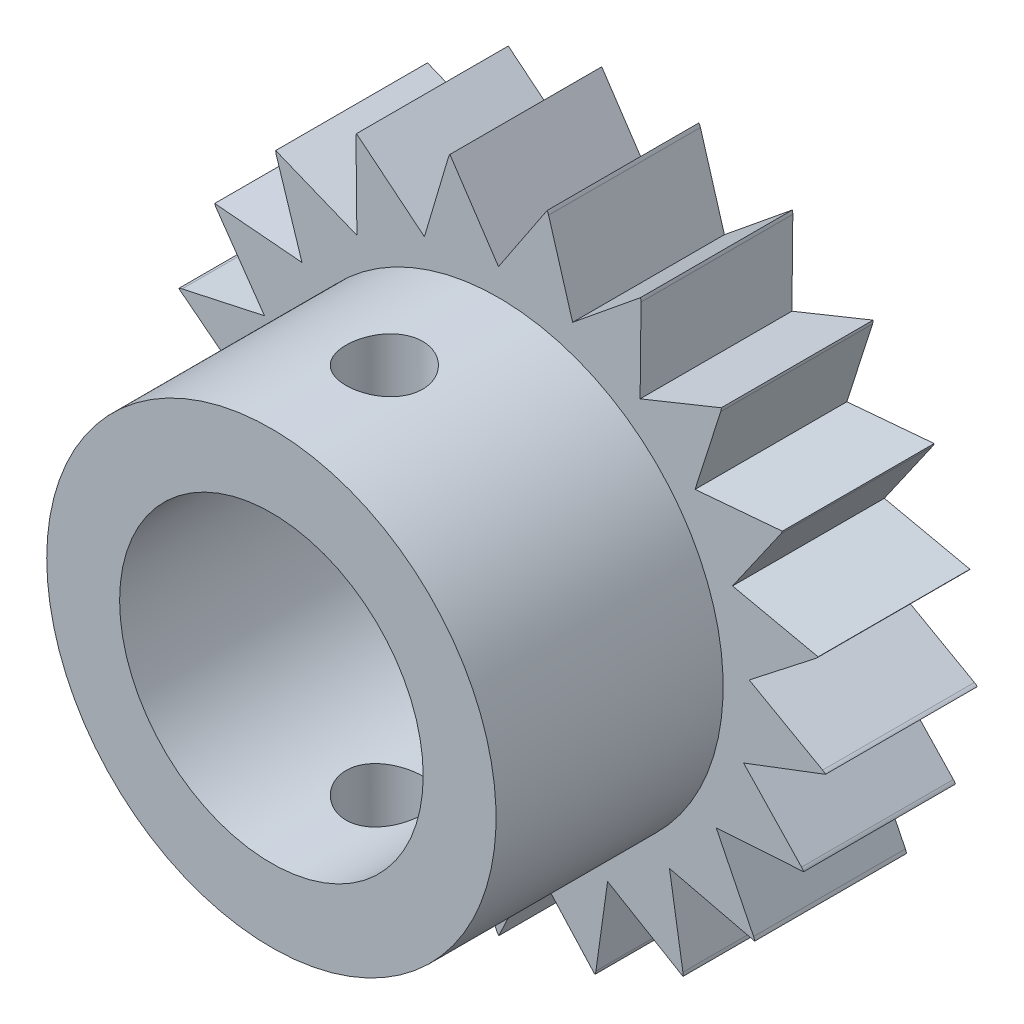
SolidWorks part; units mm, degrees
ref_plane "Front Plane" through (0, 0, 0) normal (0, 0, 1) x (1, 0, 0)
ref_plane "Top Plane" through (0, 0, 0) normal (0, 1, 0) x (1, 0, 0)
ref_plane "Right Plane" through (0, 0, 0) normal (1, 0, 0) x (0, 0, -1)
sketch "Sketch2" plane through (0, 0, 0) normal (1, 0, 0) x (0, 0, -1)
  line L0 (0, 3.175) -> (0, 6.858)
  line L1 (0, 6.858) -> (-3.175, 6.858)
  line L2 (-3.175, 6.858) -> (-3.175, 4.699)
  line L3 (-3.175, 4.699) -> (-7.9248, 4.699)
  line L4 (-7.9248, 4.699) -> (-7.9248, 3.175)
  line L5 (-7.9248, 3.175) -> (0, 3.175)
  line L6 (6.7854, 0) -> (-20.99, 0) construction
  dimension "D1" = 3.175
  dimension "D2" = 3.175
  dimension "D3" = 7.9248
  dimension "D4" = 4.699
  dimension "D5" = 6.858
revolve "Revolve1" add sketch "Sketch2" angle 360 about L6
sketch "Sketch5" plane through (0, 0, 3.175) normal (0, 0, 1) x (1, 0, 0)
  line L0 (0, 0) -> (0, 10.1517) construction
  line L1 (1.5498, 5.0242) -> (1.0283, 6.7805)
  line L2 (0, 5.2578) -> (1.016, 6.7823)
  line L3 (0, 5.2578) -> (-1.016, 6.7823)
  line L4 (1.5498, 5.0242) -> (2.97, 6.1815)
  line L5 (2.9618, 4.3442) -> (2.9812, 6.1762)
  line L6 (2.9618, 4.3442) -> (4.6601, 5.0315)
  line L7 (4.1107, 3.2782) -> (4.6692, 5.0231)
  line L8 (4.1107, 3.2782) -> (5.9361, 3.4344)
  line L9 (4.8943, 1.9209) -> (5.9423, 3.4236)
  line L10 (4.8943, 1.9209) -> (6.6847, 1.5321)
  line L11 (5.2431, 0.3929) -> (6.6874, 1.52)
  line L12 (5.2431, 0.3929) -> (6.8393, -0.5063)
  line L13 (5.126, -1.17) -> (6.8384, -0.5187)
  line L14 (5.126, -1.17) -> (6.3862, -2.4997)
  line L15 (4.5534, -2.6289) -> (6.3817, -2.5113)
  line L16 (4.5534, -2.6289) -> (5.3657, -4.271)
  line L17 (3.5762, -3.8542) -> (5.3579, -4.2807)
  line L18 (3.5762, -3.8542) -> (3.8684, -5.6629)
  line L19 (2.2813, -4.7371) -> (3.8581, -5.6698)
  line L20 (2.2813, -4.7371) -> (2.0274, -6.5515)
  line L21 (0.7836, -5.1991) -> (2.0155, -6.5551)
  line L22 (0.7836, -5.1991) -> (0.0062, -6.858)
  line L23 (-0.7836, -5.1991) -> (-0.0062, -6.858)
  line L24 (-0.7836, -5.1991) -> (-2.0155, -6.5551)
  line L25 (-2.2813, -4.7371) -> (-2.0274, -6.5515)
  line L26 (-2.2813, -4.7371) -> (-3.8581, -5.6698)
  line L27 (-3.5762, -3.8542) -> (-3.8684, -5.6629)
  line L28 (-3.5762, -3.8542) -> (-5.3579, -4.2807)
  line L29 (-4.5534, -2.6289) -> (-5.3657, -4.271)
  line L30 (-4.5534, -2.6289) -> (-6.3817, -2.5113)
  line L31 (-5.126, -1.17) -> (-6.3862, -2.4997)
  line L32 (-5.126, -1.17) -> (-6.8384, -0.5187)
  line L33 (-5.2431, 0.3929) -> (-6.8393, -0.5063)
  line L34 (-5.2431, 0.3929) -> (-6.6874, 1.52)
  line L35 (-4.8943, 1.9209) -> (-6.6847, 1.5321)
  line L36 (-4.8943, 1.9209) -> (-5.9423, 3.4236)
  line L37 (-4.1107, 3.2782) -> (-5.9361, 3.4344)
  line L38 (-4.1107, 3.2782) -> (-4.6692, 5.0231)
  line L39 (-2.9618, 4.3442) -> (-4.6601, 5.0315)
  line L40 (-2.9618, 4.3442) -> (-2.9812, 6.1762)
  line L41 (-1.5498, 5.0242) -> (-2.97, 6.1815)
  line L42 (-1.5498, 5.0242) -> (-1.0283, 6.7805)
  circle A0 centre (0, 0) radius 6.858 construction
  circle M2 centre (0, 0) radius 6.858
  dimension "D1" = 5.2578
  dimension "D2" = 1.016
  dimension "D3" = 2.032
  dimension "D4" = 21
extrude "Cut-Extrude5" cut sketch "Sketch5" against normal through all and the other way through all contours L41 L42 M2 | L39 L40 M2 | L37 L38 M2 | L35 L36 M2 | L33 L34 M2 | L31 L32 M2 | L29 L30 M2 | L27 L28 M2 | L25 L26 M2 | L23 L24 M2 | L21 L22 M2 | L19 L20 M2 | L17 L18 M2 | L15 L16 M2 | L13 L14 M2 | L11 L12 M2 | L9 L10 M2 | L7 L8 M2 | L5 L6 M2 | L1 L4 M2 | L0 L2 M2 | L3 L0 M2 region at (-0.3413, 6.3076, 3.175) region at (0.3413, 6.3076, 3.175) region at (1.8592, 6.0274, 3.175) region at (-1.8592, 6.0274, 3.175) region at (3.5532, 5.2116, 3.175) region at (-3.5532, 5.2116, 3.175) region at (4.9315, 3.9327, 3.175) region at (-4.9315, 3.9327, 3.175) region at (5.8716, 2.3044, 3.175) region at (-5.8716, 2.3044, 3.175) region at (6.29, 0.4714, 3.175) region at (-6.29, 0.4714, 3.175) region at (-6.1495, -1.4036, 3.175) region at (6.1495, -1.4036, 3.175) region at (-5.4626, -3.1538, 3.175) region at (5.4626, -3.1538, 3.175) region at (-4.2903, -4.6238, 3.175) region at (4.2903, -4.6238, 3.175) region at (-2.7368, -5.683, 3.175) region at (2.7368, -5.683, 3.175) region at (-0.9401, -6.2372, 3.175) region at (0.9401, -6.2372, 3.175)
fillet "Fillet1" radius 0.254 21 edges at (1.0283, 6.7805, 1.5875) (2.9812, 6.1762, 1.5875) (4.6692, 5.0231, 1.5875) (5.9423, 3.4236, 1.5875) (6.6874, 1.52, 1.5875) (6.8393, -0.5063, 1.5875) (6.3862, -2.4997, 1.5875) (5.3657, -4.271, 1.5875) (3.8684, -5.6629, 1.5875) (2.0274, -6.5515, 1.5875) (-0.0062, -6.858, 1.5875) (-2.0274, -6.5515, 1.5875) (-3.8684, -5.6629, 1.5875) (-5.3657, -4.271, 1.5875) (-6.3862, -2.4997, 1.5875) (-6.8393, -0.5063, 1.5875) (-1.0283, 6.7805, 1.5875) (-2.9812, 6.1762, 1.5875) (-4.6692, 5.0231, 1.5875) (-5.9423, 3.4236, 1.5875) (-6.6847, 1.5321, 1.5875)
sketch "Sketch4" plane through (0, 0, 0) normal (0, 1, 0) x (1, 0, 0)
  line L0 (-4.699, -7.9248) -> (4.699, -7.9248) construction
  circle A0 centre (0, -5.5626) radius 0.8001
  dimension "D2" = 1.6002
  dimension "D1" = 2.3622
extrude "Cut-Extrude4" cut sketch "Sketch4" against normal through all and the other way through all
